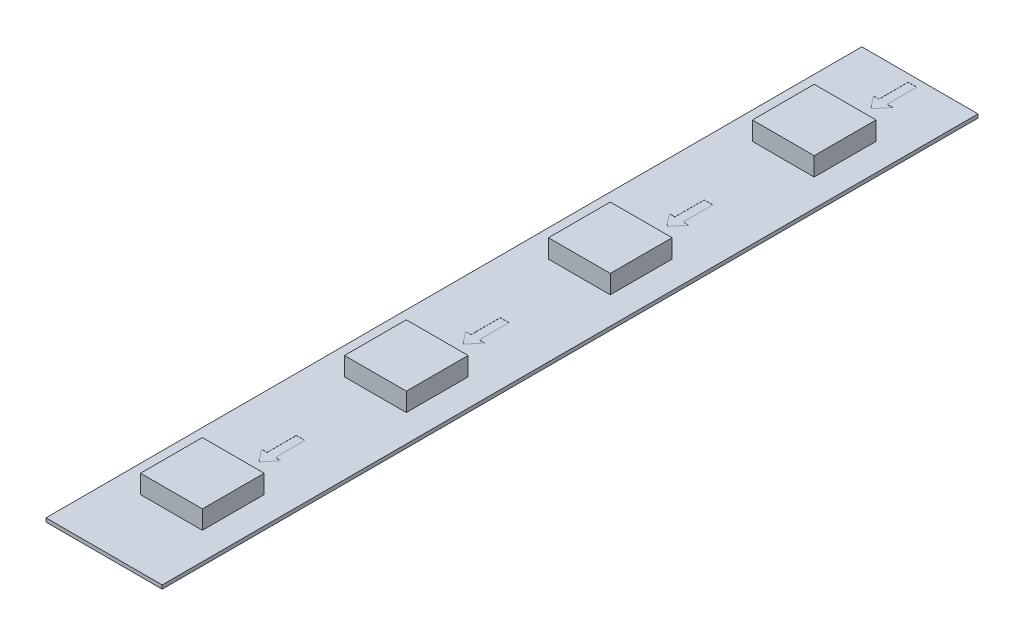
SolidWorks part; units mm, degrees
ref_plane "Front Plane" through (0, 0, 0) normal (0, 0, 1) x (1, 0, 0)
ref_plane "Top Plane" through (0, 0, 0) normal (0, 1, 0) x (1, 0, 0)
ref_plane "Right Plane" through (0, 0, 0) normal (1, 0, 0) x (0, 0, -1)
ref_axis "X-Axis" through (-88.99, 0, 0) along (1, 0, 0)
ref_axis "Y-Axis" through (0, 55, 0) along (0, -1, 0)
ref_axis "Z-Axis" through (0, 0, -88.99) along (0, 0, 1)
sketch "Sketch1" plane through (0, 0, 0) normal (0, 1, 0) x (1, 0, 0)
  line L1 (-4.7, -8.25) -> (4.7, -8.25)
  line L2 (-4.7, -8.25) -> (-4.7, 8.25)
  line L3 (-4.7, 8.25) -> (4.7, 8.25)
  line L4 (4.7, -8.25) -> (4.7, 8.25)
  line L5 (-4.7, -8.25) -> (4.7, 8.25) construction
  line L6 (-4.7, 8.25) -> (4.7, -8.25) construction
  point P0 (0, 0)
  dimension "D1" = 9.4
  dimension "D2" = 16.5
extrude "Boss-Extrude1" add sketch "Sketch1" along normal blind 0.3
sketch "Sketch2" plane through (0, 0.3, 0) normal (0, 1, 0) x (1, 0, 0)
  line L0 (0, -8.25) -> (0, 8.25) construction
  line L1 (-4.7, -8.25) -> (4.7, -8.25) construction
  line L2 (4.7, 8.25) -> (-4.7, 8.25) construction
  line L4 (-2.5, -2.8) -> (2.5, -2.8)
  line L5 (-2.5, -2.8) -> (-2.5, 2.2)
  line L6 (-2.5, 2.2) -> (2.5, 2.2)
  line L7 (2.5, -2.8) -> (2.5, 2.2)
  line L8 (-2.5, -2.8) -> (2.5, 2.2) construction
  line L9 (-2.5, 2.2) -> (2.5, -2.8) construction
  point P6 (0, -0.3)
  dimension "D1" = 5.45
  dimension "D2" = 5
  dimension "D3" = 5
extrude "Boss-Extrude2" add sketch "Sketch2" along normal blind 1.5
sketch "Sketch3" plane through (0, 0.3, 0) normal (0, 1, 0) x (1, 0, 0)
  line L0 (0, 0) -> (0, 6.4588) construction
  line L1 (-0.3478, 5.2814) -> (-0.7978, 5.2814)
  line L2 (-0.3478, 7.6512) -> (0.3522, 7.6512)
  line L3 (-0.3478, 7.6512) -> (-0.3478, 5.2814)
  line L5 (0.3522, 7.6512) -> (0.3522, 5.2512)
  line L6 (-0.3478, 7.6512) -> (0.3522, 5.2512) construction
  line L7 (-0.3478, 5.2814) -> (0.3522, 7.6512) construction
  line L8 (-0.7978, 5.2814) -> (0, 4.2814)
  line L9 (0, 4.2814) -> (0.8022, 5.2512)
  line L10 (0.8022, 5.2512) -> (0.3522, 5.2512)
  dimension "D1" = 0.45
  dimension "D2" = 0.7
  dimension "D3" = 2.4
  dimension "D4" = 1
extrude "Cut-Extrude1" cut sketch "Sketch3" against normal blind 0.01
pattern_linear "LPattern1" count 4 spacing 16.5 along (0, 0, 1) of "Cut-Extrude1", "Boss-Extrude2", "Boss-Extrude1"
